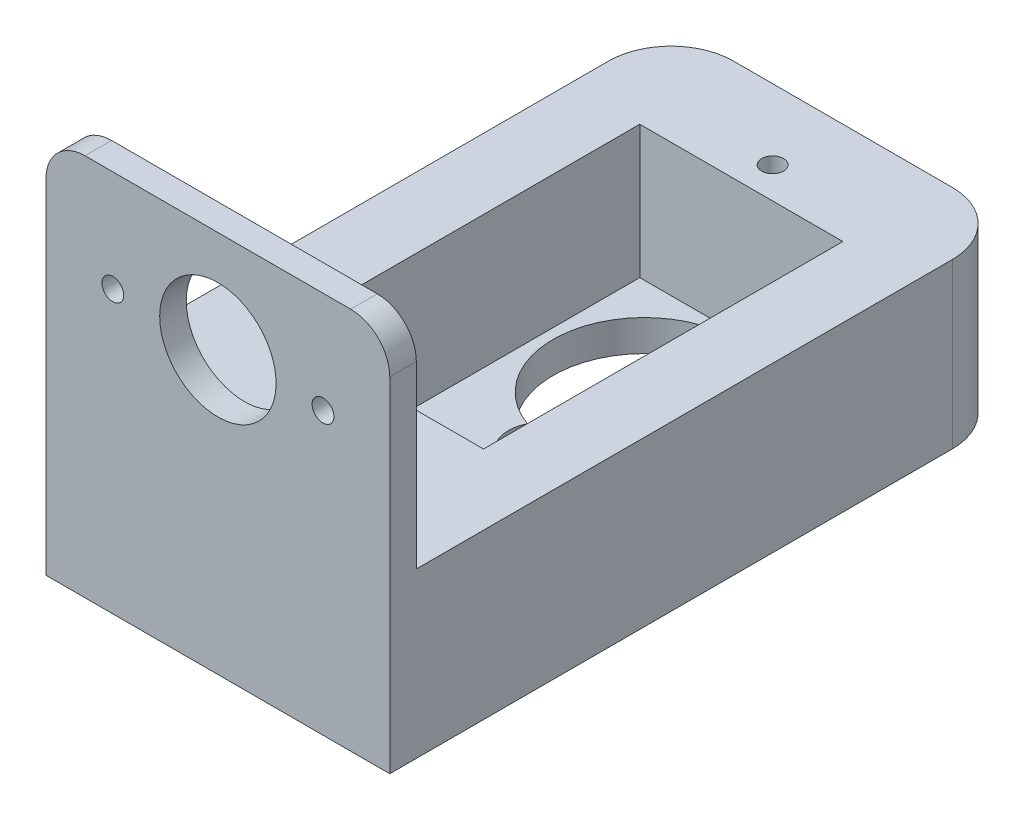
SolidWorks part; units mm, degrees
ref_plane "Front Plane" through (0, 0, 0) normal (0, 0, 1) x (1, 0, 0)
ref_plane "Top Plane" through (0, 0, 0) normal (0, 1, 0) x (1, 0, 0)
ref_plane "Right Plane" through (0, 0, 0) normal (1, 0, 0) x (0, 0, -1)
sketch "Sketch1" plane through (0, 0, 0) normal (0, 1, 0) x (1, 0, 0)
  line L1 (0, 0) -> (22, 0)
  line L2 (0, 0) -> (0, 40)
  line L3 (0, 40) -> (22, 40)
  line L4 (22, 0) -> (22, 40)
  dimension "D1" = 22
  dimension "D2" = 40
extrude "Boss-Extrude1" add sketch "Sketch1" along normal blind 10.5 contours L2 L3 L4 L1
sketch "Sketch2" plane through (0, 10.5, 0) normal (0, 1, 0) x (1, 0, 0)
  line L0 (0, 0) -> (0, 40) construction
  line L1 (4.5, 33.5) -> (17.5, 33.5)
  line L2 (4.5, 33.5) -> (4.5, 10.5)
  line L3 (4.5, 10.5) -> (17.5, 10.5)
  line L4 (17.5, 33.5) -> (17.5, 10.5)
  line L5 (0, 0) -> (22, 0) construction
  dimension "D1" = 13
  dimension "D2" = 23
  dimension "D3" = 4.5
  dimension "D4" = 10.5
extrude "Cut-Extrude1" cut sketch "Sketch2" against normal blind 8.5
sketch "Sketch3" plane through (0, 2, 0) normal (0, 1, 0) x (1, 0, 0)
  line L0 (17.5, 33.5) -> (4.5, 33.5) construction
  line L1 (17.5, 10.5) -> (17.5, 33.5) construction
  circle A0 centre (11, 27.3) radius 5.85
  dimension "D1" = 6.2
  dimension "D3" = 11.7
  dimension "D2" = 6.5
extrude "Cut-Extrude2" cut sketch "Sketch3" against normal through all
sketch "Sketch4" plane through (0, 10.5, 0) normal (0, 1, 0) x (1, 0, 0)
  line L0 (0, 0) -> (0, 40) construction
  line L1 (0, 1.7) -> (22, 1.7)
  line L2 (0, 1.7) -> (0, 0)
  line L3 (0, 0) -> (22, 0)
  line L4 (22, 1.7) -> (22, 0)
  dimension "D1" = 1.7
extrude "Boss-Extrude2" add sketch "Sketch4" along normal blind 14
sketch "Sketch5" plane through (0, 0, -1.7) normal (0, 0, -1) x (-1, 0, 0)
  line L0 (-22, 24.5) -> (-22, 10.5) construction
  line L1 (-22, 10.5) -> (0, 10.5) construction
  circle A0 centre (-11, 18) radius 3.725
  circle A3 centre (-17.725, 18) radius 0.7
  circle A4 centre (-4.275, 18) radius 0.7
  dimension "D1" = 7.45
  dimension "D2" = 3
  dimension "D5" = 7.5
  dimension "D3" = 3
  dimension "D4" = 11
extrude "Cut-Extrude3" cut sketch "Sketch5" against normal through all contours A0
extrude "Cut-Extrude4" cut sketch "Sketch5<3>" against normal blind 10
sketch "Sketch5<3>" plane through (0, 0, -1.7) normal (0, 0, -1) x (-1, 0, 0) same geometry as "Sketch5"
sketch "Sketch6" plane through (0, 10.5, 0) normal (0, 1, 0) x (1, 0, 0)
  line L0 (17.5, 33.5) -> (4.5, 33.5) construction
  line L1 (4.5, 10.5) -> (17.5, 10.5) construction
  circle A0 centre (11, 35.5) radius 0.7
  circle A1 centre (11, 7.5) radius 0.7
  dimension "D1" = 2
  dimension "D2" = 1.4
  dimension "D3" = 3
extrude "Cut-Extrude5" cut sketch "Sketch6" against normal blind 2.5
fillet "Fillet1" radius 4 2 edges at (0, 5.25, -40) (22, 5.25, -40)
fillet "Fillet2" radius 2.5 2 edges at (0, 24.5, -0.85) (22, 24.5, -0.85)
sketch "Sketch7" plane through (0, 2, 0) normal (0, 1, 0) x (1, 0, 0)
  arc A0 (9.0237, 21.8334) -> (12.8034, 21.7841) centre (10.9008, 20.8287) ccw
  arc A2 (9.0237, 21.8334) -> (12.8034, 21.7841) centre (10.9856, 27.3317) ccw
  point P4 (0, 0)
  point P5 (9.0237, 21.8334)
  point P6 (12.3828, 21.7187)
  point P7 (9.4059, 21.7754)
  point P8 (9.3588, 21.6849)
  point P9 (8.472, 21.8662)
  point P10 (8.9991, 21.708)
  point P11 (0, 0)
  point P12 (0, 0)
  point P13 (12.7982, 21.7332)
  point P14 (9.0102, 21.7988)
  point P15 (12.8077, 21.7363)
  point P16 (12.8034, 21.7841)
extrude "Cut-Extrude6" cut sketch "Sketch7" against normal blind 10
